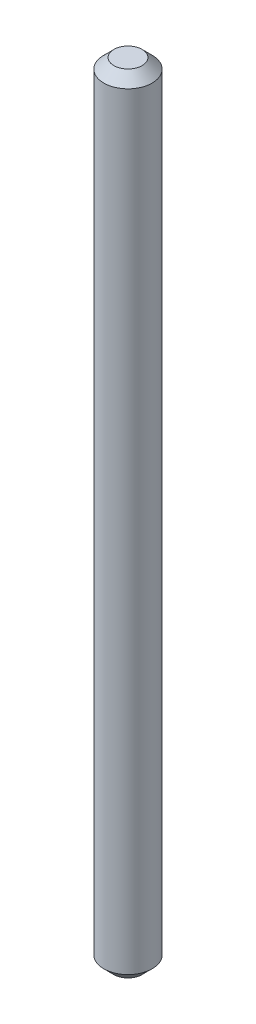
SolidWorks part; units mm, degrees
material "6061 Alloy"
ref_plane "Front" through (0, 0, 0) normal (0, 0, 1) x (1, 0, 0)
ref_plane "Top" through (0, 0, 0) normal (0, 1, 0) x (1, 0, 0)
ref_plane "Right" through (0, 0, 0) normal (1, 0, 0) x (0, 0, -1)
sketch "Sketch1" plane through (0, 0, 0) normal (0, 1, 0) x (1, 0, 0)
  circle A0 centre (0, 0) radius 3.048
  dimension "D1" = 6.096
extrude "Boss-Extrude1" add sketch "Sketch1" along normal blind 99.294
chamfer "Chamfer1" distance 1.27 angle 45 1 edges at (0, 99.294, 3.048)
chamfer "Chamfer2" distance 1.27 angle 45 1 edges at (0, 0, 3.048)
